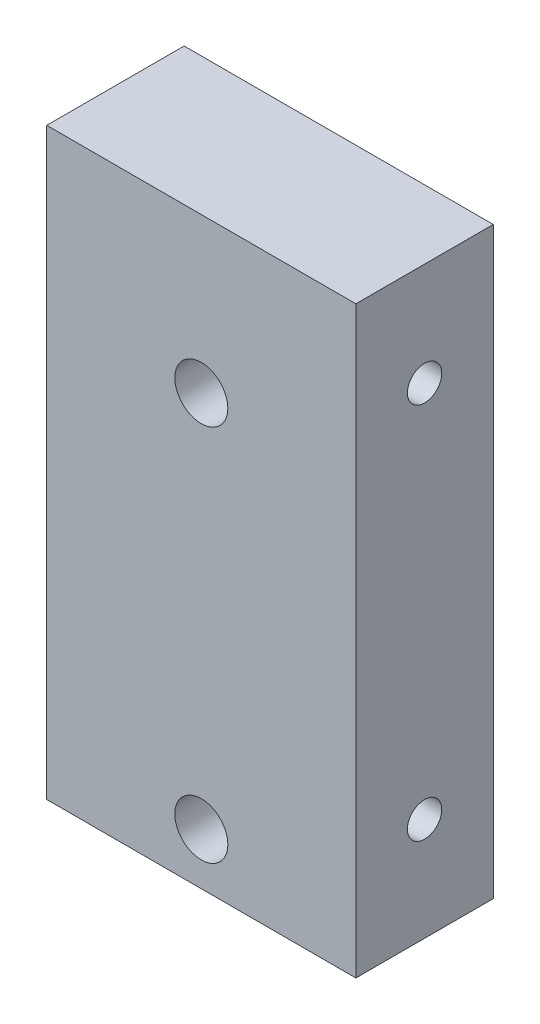
SolidWorks part; units mm, degrees
material "6061-T6 (SS)"
ref_plane "Front" through (0, 0, 0) normal (0, 0, 1) x (1, 0, 0)
ref_plane "Top" through (0, 0, 0) normal (0, 1, 0) x (1, 0, 0)
ref_plane "Right" through (0, 0, 0) normal (1, 0, 0) x (0, 0, -1)
sketch "Sketch1" plane through (0, 0, 0) normal (0, 1, 0) x (1, 0, 0)
  line L1 (-28.575, -12.7) -> (28.575, -12.7)
  line L2 (-28.575, -12.7) -> (-28.575, 12.7)
  line L3 (-28.575, 12.7) -> (28.575, 12.7)
  line L4 (28.575, -12.7) -> (28.575, 12.7)
  line L5 (-28.575, -12.7) -> (28.575, 12.7) construction
  line L6 (-28.575, 12.7) -> (28.575, -12.7) construction
  line L11 (-19.05, -19.05) -> (19.05, 19.05) construction
  line L12 (-19.05, 19.05) -> (19.05, -19.05) construction
  point P0 (0, 0)
  point P5 (0, 0)
  dimension "D1" = 25.4
  dimension "D2" = 57.15
extrude "Boss-Extrude1" add sketch "Sketch1" along normal mid plane 107.95
sketch "Sketch2" plane through (28.575, 0, 0) normal (1, 0, 0) x (0, 0, -1)
  line L0 (0, 53.975) -> (0, 34.925) construction
  line L1 (-12.7, 53.975) -> (12.7, 53.975) construction
  line L2 (0, 34.925) -> (0, -34.925) construction
  line L3 (0, -34.925) -> (0, -53.975) construction
  line L4 (-12.7, -53.975) -> (12.7, -53.975) construction
  dimension "D2" = 69.85
hole_wizard "1/4 (0.25) Diameter Hole1" positions "Sketch4" profile "Sketch3" hole size "1/4" standard "ANSI Inch" end condition through all
sketch "Sketch4" plane through (28.575, 0, 0) normal (1, 0, 0) x (0, 0, -1)
  point P0 (0, -34.925)
  point P3 (0, 34.925)
sketch "Sketch3" plane through (28.575, -34.925, 0) normal (0, 1, 0) x (0, 0, -1)
  line L0 (0, 0) -> (0, 57.15)
  line L1 (0, 57.15) -> (3.175, 57.15)
  line L2 (3.175, 57.15) -> (3.175, 0)
  line L5 (3.175, 0) -> (0, 0)
  line L11 (0, -6.35) -> (0, 107.95) construction
  dimension "Thru Hole Dia." = 6.35
  dimension "Thru Hole Depth" = 57.15
sketch "Sketch5" plane through (0, 0, 12.7) normal (0, 0, 1) x (1, 0, 0)
  line L0 (0, -53.975) -> (0, -44.45) construction
  line L1 (-28.575, -53.975) -> (28.575, -53.975) construction
  line L2 (0, -44.45) -> (0, 25.4) construction
  line L3 (0, 25.4) -> (0, 53.975) construction
  line L4 (-28.575, 53.975) -> (28.575, 53.975) construction
  dimension "D1" = 69.85
  dimension "D2" = 9.525
hole_wizard "3/8 Clearance Hole1" positions "Sketch7" profile "Sketch6" hole size "3/8" standard "ANSI Inch" end condition through all
sketch "Sketch7" plane through (0, 0, 12.7) normal (0, 0, 1) x (1, 0, 0)
  point P0 (0, -44.45)
  point P3 (0, 25.4)
sketch "Sketch6" plane through (0, -44.45, 12.7) normal (1, 0, 0) x (0, -1, 0)
  line L0 (0, 0) -> (0, 25.4)
  line L1 (0, 25.4) -> (4.9022, 25.4)
  line L2 (4.9022, 25.4) -> (4.9022, 0)
  line L5 (4.9022, 0) -> (0, 0)
  line L11 (0, -6.35) -> (0, 107.95) construction
  dimension "Thru Hole Dia." = 9.8044
  dimension "Thru Hole Depth" = 25.4
